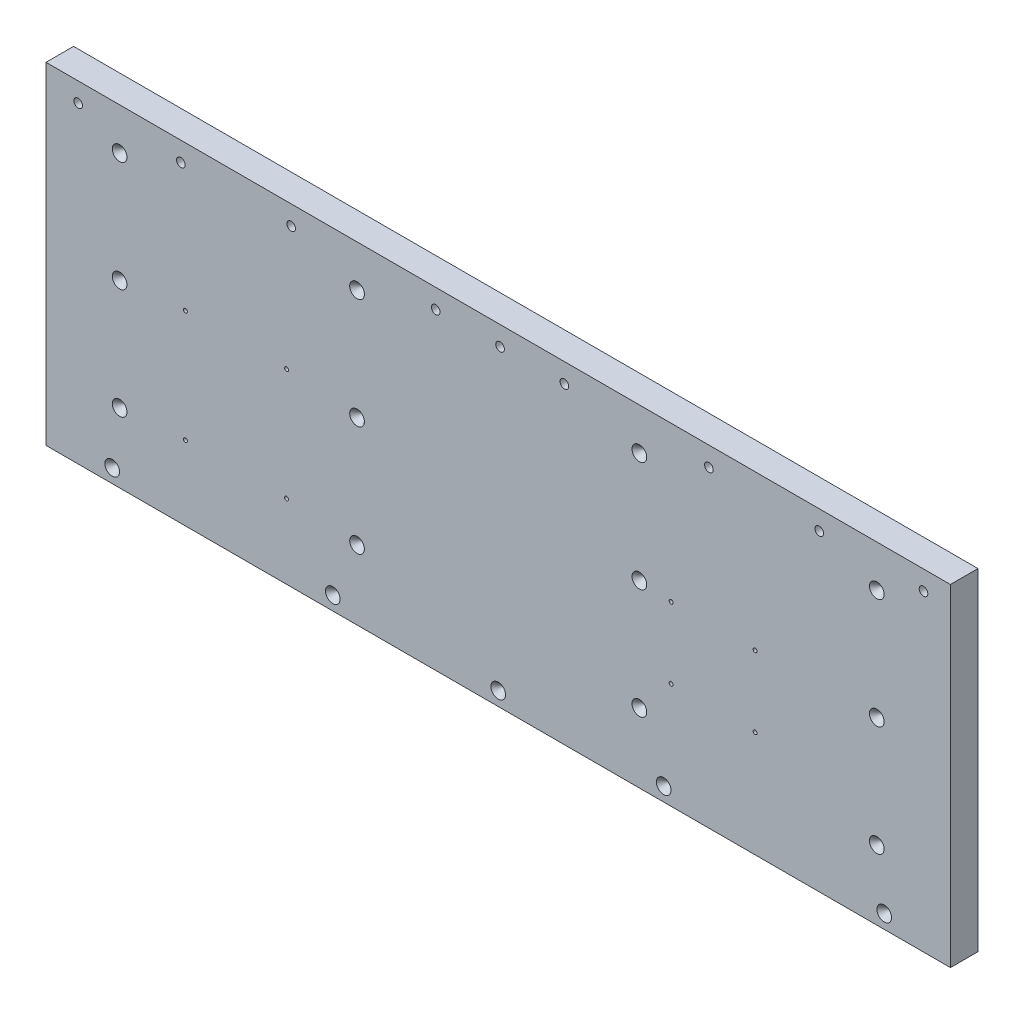
SolidWorks part; units mm, degrees
material "MDF"
ref_plane "Front Plane" through (0, 0, 0) normal (0, 0, 1) x (1, 0, 0)
ref_plane "Top Plane" through (0, 0, 0) normal (0, 1, 0) x (1, 0, 0)
ref_plane "Right Plane" through (0, 0, 0) normal (1, 0, 0) x (0, 0, -1)
sketch "Sketch1" plane through (0, 0, 0) normal (0, 0, 1) x (1, 0, 0)
  line L0 (128.7463, -697.8385) -> (128.7463, -132.715) construction
  line L1 (-496.0937, -132.715) -> (128.7463, -132.715)
  line L2 (-496.0937, -132.715) -> (-496.0937, -361.95)
  line L3 (-496.0937, -361.95) -> (128.7463, -361.95)
  line L4 (128.7463, -132.715) -> (128.7463, -361.95)
  line L5 (-496.0937, -132.715) -> (-496.0937, -697.8385) construction
  line L12 (128.7463, -132.715) -> (-84.6137, -132.715) construction
  line L13 (-290.722, -342.9) -> (-271.672, -342.9) construction
  dimension "D1" = 19.05
extrude "Boss-Extrude1" add sketch "Sketch1" along normal blind 19.05
hole_wizard "5/64 (0.07813) Diameter Hole1" positions "Sketch5" profile "Sketch6" hole size "5/64" standard "ANSI Inch"
sketch "Sketch5" plane through (-182.4037, -6471.4599, 19.05) normal (0, 0, 1) x (1, 0, 0)
  line L1 (-1.27, 6109.5099) -> (-1.27, 6338.7449) construction
  point P0 (-262.8265, 6157.4524)
  point P6 (-98.7933, 6157.4524)
  point P18 (-262.8265, 6233.6524)
  point P19 (-98.7933, 6233.6524)
  point P22 (-262.8265, 6309.8524)
  point P23 (-98.7933, 6309.8524)
  point P24 (-267.97, 6119.0349)
  point P34 (-115.57, 6119.0349)
  point P37 (-1.27, 6119.0349)
  point P40 (113.03, 6119.0349)
  point P44 (265.43, 6119.0349)
  point P55 (96.2533, 6309.8524)
  point P56 (260.2865, 6309.8524)
  point P59 (96.2533, 6233.6524)
  point P60 (260.2865, 6233.6524)
  point P63 (96.2533, 6157.4524)
  point P64 (260.2865, 6157.4524)
sketch "Sketch6" plane through (-445.2302, -314.0075, 19.05) normal (1, 0, 0) x (0, -1, 0)
  line L0 (0, 0) -> (0, 38.6962)
  line L1 (0, 38.6962) -> (0.9923, 38.1)
  line L2 (0.9923, 38.1) -> (0.9923, 4.7024)
  line L3 (0.9923, 4.7024) -> (5.08, 0)
  line L4 (5.08, 0) -> (0, 0)
  line L5 (-0.9923, 4.7024) -> (-5.08, 0) construction
  line L6 (0, 38.6962) -> (-0.9923, 38.1) construction
  line L7 (0, -6.35) -> (0, 107.95) construction
  dimension "Hole Dia." = 1.9845
  dimension "Hole Depth" = 38.1
  dimension "Near C'Sink Dia." = 10.16
  dimension "Near C'Sink Angle" = 82
  dimension "Drill Angle" = 118
hole_wizard "15/64 (0.23438) Diameter Hole1" positions "Sketch7" profile "Sketch8" hole size "15/64" standard "ANSI Inch" end condition up to next
sketch "Sketch7" plane through (0, 0, 0) normal (0, 0, -1) x (-1, 0, 0)
  point P0 (402.9075, -146.05)
  point P2 (326.7075, -146.05)
  point P4 (226.8537, -146.05)
  point P6 (182.4037, -146.05)
  point P8 (137.9537, -146.05)
  point P10 (38.1, -146.05)
  point P12 (-38.1, -146.05)
  point P13 (473.8687, -146.05)
  point P17 (-110.1471, -146.05)
sketch "Sketch8" plane through (-402.9075, -146.05, 0) normal (1, 0, 0) x (0, 1, 0)
  line L0 (0, 0) -> (0, 19.05)
  line L1 (0, 19.05) -> (2.9766, 19.05)
  line L2 (2.9766, 19.05) -> (2.9766, 0)
  line L5 (2.9766, 0) -> (0, 0)
  line L11 (0, -6.35) -> (0, 107.95) construction
  dimension "Thru Hole Dia." = 5.9533
  dimension "Thru Hole Depth" = 19.05
sketch "Sketch9" plane through (0, 0, 0) normal (0, 0, -1) x (-1, 0, 0)
  line L0 (0, -157.1498) -> (0, -342.9) construction
  line L1 (0, -250.0249) -> (93.1355, -250.0249) construction
  line L2 (61.3728, -330.2) -> (-61.3728, -330.2)
  line L3 (61.3728, -330.2) -> (61.3728, -169.8498)
  line L4 (61.3728, -169.8498) -> (-61.3728, -169.8498)
  line L5 (-61.3728, -330.2) -> (-61.3728, -169.8498)
  line L6 (61.3728, -330.2) -> (-61.3728, -169.8498) construction
  line L7 (61.3728, -169.8498) -> (-61.3728, -330.2) construction
  line L8 (93.1355, -250.0249) -> (271.672, -250.0249) construction
  line L9 (364.8075, -157.1625) -> (364.8075, -342.9) construction
  line L10 (258.972, -330.2) -> (105.8355, -330.2)
  line L11 (258.972, -330.2) -> (258.972, -169.8498)
  line L12 (258.972, -169.8498) -> (105.8355, -169.8498)
  line L13 (105.8355, -330.2) -> (105.8355, -169.8498)
  line L14 (258.972, -330.2) -> (105.8355, -169.8498) construction
  line L15 (258.972, -169.8498) -> (105.8355, -330.2) construction
  line L17 (426.1802, -330.2127) -> (303.4347, -330.2127)
  line L18 (426.1802, -330.2127) -> (426.1802, -169.8498)
  line L19 (426.1802, -169.8498) -> (303.4347, -169.8498)
  line L20 (303.4347, -330.2127) -> (303.4347, -169.8498)
  line L21 (426.1802, -330.2127) -> (303.4347, -169.8498) construction
  line L22 (426.1802, -169.8498) -> (303.4347, -330.2127) construction
  point P3 (0, -250.0249)
  point P8 (-74.0728, -342.9)
  point P13 (182.4037, -250.0249)
  point P20 (364.8075, -250.0313)
  dimension "D1" = 12.7
  dimension "D2" = 12.7
  dimension "D3" = 12.7
extrude "Cut-Extrude1" [suppressed] cut sketch "Sketch9" against normal up to next
fillet "Fillet1" [suppressed] radius 12.7
hole_wizard "#2 Clearance Hole1" positions "Sketch10" profile "Sketch11" hole size "#2" standard "ANSI Inch" end condition up to next
sketch "Sketch10" plane through (0, 0, 19.05) normal (0, 0, 1) x (1, 0, 0)
  point P2 (-6.2354, -239.6)
  point P4 (-64.2354, -239.6)
  point P6 (-64.2354, -288.6)
  point P8 (-6.2354, -288.6)
sketch "Sketch11" plane through (-6.2354, -239.6, 19.05) normal (1, 0, 0) x (0, -1, 0)
  line L0 (0, 0) -> (0, 19.05)
  line L1 (0, 19.05) -> (1.3525, 19.05)
  line L2 (1.3525, 19.05) -> (1.3525, 0)
  line L5 (1.3525, 0) -> (0, 0)
  line L11 (0, -6.35) -> (0, 107.95) construction
  dimension "Thru Hole Dia." = 2.7051
  dimension "Thru Hole Depth" = 19.05
hole_wizard "#2 Clearance Hole2" positions "Sketch12" profile "Sketch13" hole size "#2" standard "ANSI Inch" end condition up to next
sketch "Sketch12" plane through (0, 0, 0) normal (0, 0, -1) x (-1, 0, 0)
  point P0 (399.7261, -233.172)
  point P2 (329.8761, -233.172)
  point P4 (329.8761, -310.642)
  point P6 (399.7261, -310.642)
sketch "Sketch13" plane through (-399.7261, -233.172, 0) normal (1, 0, 0) x (0, 1, 0)
  line L0 (0, 0) -> (0, 19.05)
  line L1 (0, 19.05) -> (1.3525, 19.05)
  line L2 (1.3525, 19.05) -> (1.3525, 0)
  line L5 (1.3525, 0) -> (0, 0)
  line L11 (0, -6.35) -> (0, 107.95) construction
  dimension "Thru Hole Dia." = 2.7051
  dimension "Thru Hole Depth" = 19.05
